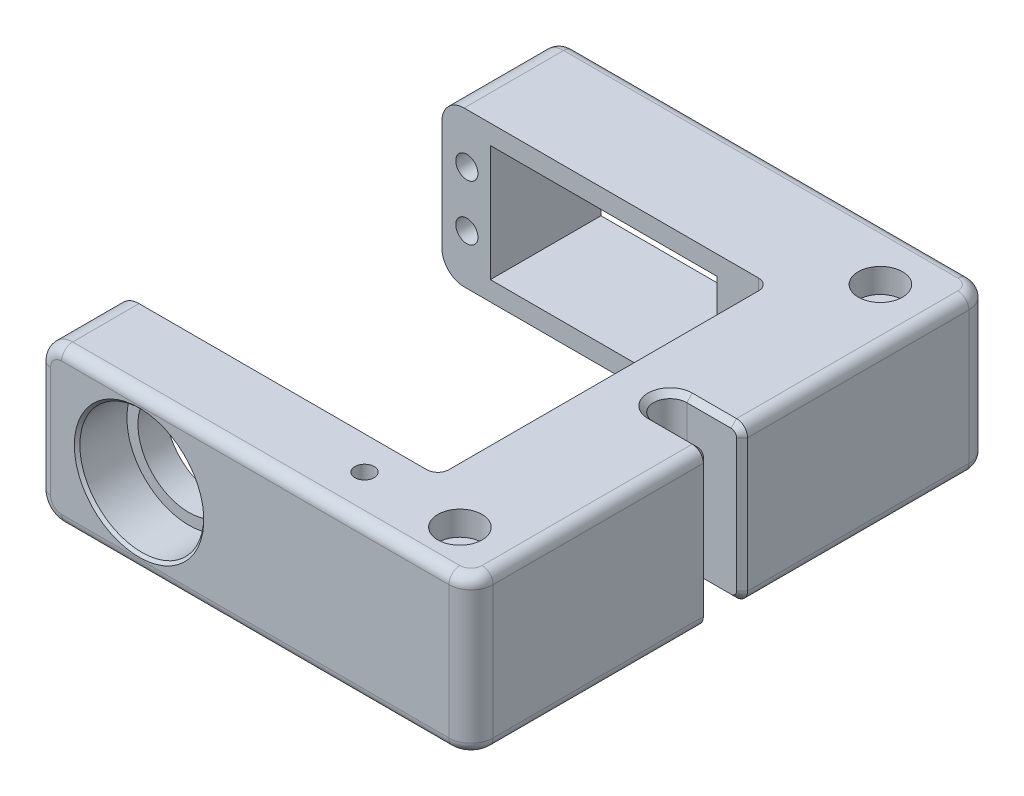
SolidWorks part; units mm, degrees
ref_plane "Top Plane" through (0, 0, 0) normal (0, 0, 1) x (1, 0, 0)
ref_plane "Right Plane" through (0, 0, 0) normal (0, 1, 0) x (1, 0, 0)
ref_plane "Front Plane" through (0, 0, 0) normal (1, 0, 0) x (0, 0, -1)
sketch "Sketch1" plane through (0, 0, 0) normal (0, 0, 1) x (1, 0, 0)
  line L0 (-10, 0) -> (30, 0) construction
  line L1 (-10, 10) -> (30, 10) construction
  line L2 (-10, 10) -> (-10, -10) construction
  line L3 (-10, -10) -> (30, -10) construction
  line L4 (30, 10) -> (30, -10) construction
  line L5 (-10, 10) -> (-17.25, 10) construction
  line L6 (-17.25, 10) -> (-17.25, -10) construction
  line L7 (-17.25, -10) -> (-10, -10) construction
  line L8 (10, 10) -> (10, -10) construction
  line L9 (37.25, -10) -> (30, -10) construction
  line L10 (37.25, 10) -> (37.25, -10) construction
  line L11 (30, 10) -> (37.25, 10) construction
  line L12 (40, 14) -> (40, -14) construction
  line L13 (-19.25, 14) -> (60, 14)
  line L14 (-19.25, 14) -> (-19.25, -14)
  line L15 (-19.25, -14) -> (60, -14)
  line L16 (60, 14) -> (60, -14)
  circle A0 centre (0, 0) radius 11 construction
  circle A1 centre (0, 0) radius 4 construction
  circle A2 centre (-14.75, 5) radius 2 construction
  circle A3 centre (-14.75, -5) radius 2 construction
  circle A4 centre (34.75, -5) radius 2 construction
  circle A5 centre (34.75, 5) radius 2 construction
  dimension "D1" = 22
  dimension "D2" = 8
  dimension "D12" = 4
  dimension "D3" = 40
  dimension "D4" = 20
  dimension "D5" = 54.5
  dimension "D6" = 37.25
  dimension "D7" = 20
  dimension "D8" = 40
  dimension "D9" = 14
  dimension "D10" = 14
  dimension "D11" = 2
  dimension "D13" = 10
  dimension "D14" = 49.5
extrude "Boss-Extrude1" add sketch "Sketch1" along normal blind 20
sketch "Sketch2" plane through (0, 0, 20) normal (0, 0, 1) x (1, 0, 0)
  line L1 (40, 14) -> (60, 14)
  line L2 (40, 14) -> (40, -14)
  line L3 (40, -14) -> (60, -14)
  line L4 (60, 14) -> (60, -14)
extrude "Boss-Extrude2" add sketch "Sketch2" along normal blind 60
sketch "Sketch3" plane through (0, 0, 80) normal (0, 0, 1) x (1, 0, 0)
  line L0 (-19.25, -14) -> (60, -14) construction
  line L1 (60, 14) -> (-18, 14)
  line L2 (60, 14) -> (60, -14)
  line L3 (60, -14) -> (-18, -14)
  line L4 (-18, 14) -> (-18, -14)
  dimension "D1" = 18
extrude "Boss-Extrude3" add sketch "Sketch3" along normal blind 14
sketch "Sketch4" plane through (0, 0, 20) normal (0, 0, 1) x (1, 0, 0)
  line L8 (-10.5, -10.5) -> (30.5, -10.5)
  line L9 (30.5, -10.5) -> (30.5, 10.5)
  line L10 (30.5, 10.5) -> (-10.5, 10.5)
  line L11 (-10.5, 10.5) -> (-10.5, -10.5)
  line L12 (-10.5, -10.5) -> (30.5, -10.5)
  line L13 (30.5, -10.5) -> (30.5, 10.5)
  line L14 (30.5, 10.5) -> (-10.5, 10.5)
  line L15 (-10.5, 10.5) -> (-10.5, -10.5)
  dimension "D1" = 0.5
extrude "Cut-Extrude1" cut sketch "Sketch4" against normal through all
sketch "Sketch5" plane through (0, 0, 20) normal (0, 0, 1) x (1, 0, 0)
  circle A0 centre (34.75, -5) radius 2 construction
  circle A1 centre (34.75, 5) radius 2 construction
  circle A2 centre (-14.75, -5) radius 2 construction
  circle A3 centre (-14.75, 5) radius 2 construction
  circle A4 centre (34.75, -5) radius 2
  circle A5 centre (34.75, 5) radius 2
  circle A6 centre (-14.75, -5) radius 2
  circle A7 centre (-14.75, 5) radius 2
extrude "Cut-Extrude2" cut sketch "Sketch5" against normal through all
sketch "Sketch6" plane through (0, 0, 0) normal (0, 0, -1) x (-1, 0, 0)
  line L0 (-10, 10.5) -> (-10, -10.5) construction
  line L1 (-34.75, 8.4641) -> (-37.75, 6.7321)
  line L2 (-37.75, 6.7321) -> (-37.75, 3.2679)
  line L3 (-37.75, 3.2679) -> (-34.75, 1.5359)
  line L4 (-34.75, 1.5359) -> (-31.75, 3.2679)
  line L5 (-31.75, 3.2679) -> (-31.75, 6.7321)
  line L6 (-31.75, 6.7321) -> (-34.75, 8.4641)
  line L7 (-34.75, -1.5359) -> (-37.75, -3.2679)
  line L8 (-37.75, -3.2679) -> (-37.75, -6.7321)
  line L9 (-37.75, -6.7321) -> (-34.75, -8.4641)
  line L10 (-34.75, -8.4641) -> (-31.75, -6.7321)
  line L11 (-31.75, -6.7321) -> (-31.75, -3.2679)
  line L12 (-31.75, -3.2679) -> (-34.75, -1.5359)
  line L13 (-30.5, 10.5) -> (10.5, 10.5) construction
  line L14 (10.5, -10.5) -> (-30.5, -10.5) construction
  line L15 (11.75, -3.2679) -> (14.75, -1.5359)
  line L16 (11.75, -6.7321) -> (11.75, -3.2679)
  line L17 (14.75, -8.4641) -> (11.75, -6.7321)
  line L18 (17.75, -6.7321) -> (14.75, -8.4641)
  line L19 (17.75, -3.2679) -> (17.75, -6.7321)
  line L20 (14.75, -1.5359) -> (17.75, -3.2679)
  line L21 (11.75, 6.7321) -> (14.75, 8.4641)
  line L22 (11.75, 3.2679) -> (11.75, 6.7321)
  line L23 (14.75, 1.5359) -> (11.75, 3.2679)
  line L24 (17.75, 3.2679) -> (14.75, 1.5359)
  line L25 (17.75, 6.7321) -> (17.75, 3.2679)
  line L26 (14.75, 8.4641) -> (17.75, 6.7321)
  circle A0 centre (-34.75, 5) radius 3 construction
  circle A1 centre (-34.75, -5) radius 3 construction
  circle A2 centre (14.75, -5) radius 3 construction
  circle A3 centre (14.75, 5) radius 3 construction
  dimension "D1" = 6
extrude "Cut-Extrude3" cut sketch "Sketch6" against normal offset from surface (14 mm away) 6 up to face at (36.75, 5, 20)
sketch "Sketch7" plane through (0, 0, 94) normal (0, 0, 1) x (1, 0, 0)
  circle A2 centre (0, 0) radius 11.2
  circle A3 centre (0, 0) radius 11.2
  dimension "D1" = 0.2
extrude "Cut-Extrude4" cut sketch "Sketch7" against normal blind 9
sketch "Sketch8" plane through (0, 0, 85) normal (0, 0, 1) x (1, 0, 0)
  circle A0 centre (0, 0) radius 9.2
  circle A1 centre (0, 0) radius 11.2 construction
  dimension "D1" = 2
extrude "Cut-Extrude5" cut sketch "Sketch8" against normal up to next
sketch "Sketch12" plane through (0, 14, 0) normal (0, 1, 0) x (1, 0, 0)
  line L0 (60, 0) -> (-19.25, 0) construction
  line L1 (60, -94) -> (60, 0) construction
  line L2 (60, -94) -> (-18, -94) construction
  circle A0 centre (50, -10) radius 2 construction
  circle A1 centre (50, -10) radius 3.75 construction
  circle A2 centre (50, -86) radius 2 construction
  circle A3 centre (50, -86) radius 3.75 construction
  dimension "D1" = 4
  dimension "D2" = 7.5
  dimension "D5" = 8
  dimension "D3" = 10
  dimension "D4" = 10
  dimension "D6" = 10
hole_wizard "CBORE for M4 Hex Socket Head Cap Screw1" positions "Sketch13" profile "Sketch14" counterbore size "M4" standard "ISO" end condition through all
sketch "Sketch13" plane through (0, 14, 0) normal (0, 1, 0) x (1, 0, 0)
  point P2 (50, -10)
  point P7 (50, -86)
sketch "Sketch14" plane through (50, 14, 10) normal (1, 0, 0) x (0, 0, 1)
  line L0 (0, 0) -> (0, 28)
  line L1 (0, 28) -> (2.15, 28)
  line L3 (2.15, 28) -> (2.15, 4.4)
  line L4 (2.15, 4.4) -> (4, 4.4)
  line L5 (4, 4.4) -> (4, 0)
  line L7 (4, 0) -> (0, 0)
  line L11 (0, -6.35) -> (0, 107.95) construction
  dimension "Thru Hole Dia." = 4.3
  dimension "Thru Hole Depth" = 28
  dimension "C'Bore Dia." = 8
  dimension "C'Bore Depth" = 4.4
sketch "Sketch15" plane through (0, 14, 0) normal (0, 1, 0) x (1, 0, 0)
  line L0 (32.75, -86) -> (50, -86) construction
  circle A0 centre (32.75, -86) radius 1.75
  dimension "D1" = 17.25
  dimension "D2" = 3.5
extrude "Cut-Extrude6" cut sketch "Sketch15" against normal through all
sketch "Sketch16" plane through (0, -14, 0) normal (0, -1, 0) x (1, 0, 0)
  line L1 (31.0179, 89) -> (29.2859, 86)
  line L2 (29.2859, 86) -> (31.0179, 83)
  line L3 (31.0179, 83) -> (34.4821, 83)
  line L4 (34.4821, 83) -> (36.2141, 86)
  line L5 (36.2141, 86) -> (34.4821, 89)
  line L6 (34.4821, 89) -> (31.0179, 89)
  circle A0 centre (32.75, 86) radius 3 construction
  dimension "D1" = 6
extrude "Cut-Extrude7" cut sketch "Sketch16" against normal blind 5
sketch "Sketch17" plane through (0, 14, 0) normal (0, 1, 0) x (1, 0, 0)
  line L0 (50, -10) -> (50, -86) construction
  line L1 (50, -45) -> (60, -45)
  line L2 (60, -94) -> (60, 0) construction
  line L3 (50, -51) -> (60, -51)
  line L4 (60, -45) -> (60, -51)
  arc A0 (50, -45) -> (50, -51) centre (50, -48) ccw
  dimension "D1" = 6
  dimension "D2" = 38
extrude "Cut-Extrude8" cut sketch "Sketch17" against normal through all
fillet "Fillet6" radius 0.5 7 edges at (32.75, -9, 84.25) (30.1519, -9, 84.5) (32.75, -9, 83) (35.3481, -9, 84.5) (35.3481, -9, 87.5) (32.75, -9, 89) (30.1519, -9, 87.5)
fillet "Fillet1" radius 4 4 edges at (-18, -14, 87) (-18, 14, 87) (-19.25, -14, 10) (-19.25, 14, 10)
fillet "Fillet3" radius 4 2 edges at (60, 0, 0) (60, 0, 94)
fillet "Fillet4" radius 2 2 edges at (40, 0, 20) (40, 0, 80)
fillet "Fillet5" radius 2 16 edges at (58.8284, -14, 92.8284) (21, -14, 94) (-16.8284, -12.8284, 94) (-18, 0, 94) (-16.8284, 12.8284, 94) (21, 14, 94) (58.8284, 14, 92.8284) (60, 14, 24.5) (58.8284, 14, 1.1716) (20.375, 14, 0) (-18.0784, 12.8284, 0) (-19.25, 0, 0) (-18.0784, -12.8284, 0) (20.375, -14, 0) (58.8284, -14, 1.1716) (60, -14, 24.5)
chamfer "Chamfer1" distance 0.5 angle 45 1 edges at (11.2, 0, 94)
chamfer "Chamfer2" distance 1 angle 45 12 edges at (47, 14, 48) (47, -14, 48) (54, -14, 45) (54, -14, 51) (59.4142, -13.4142, 51) (60, 0, 51) (59.4142, 13.4142, 51) (54, 14, 45) (54, 14, 51) (59.4142, -13.4142, 45) (60, 0, 45) (59.4142, 13.4142, 45)
